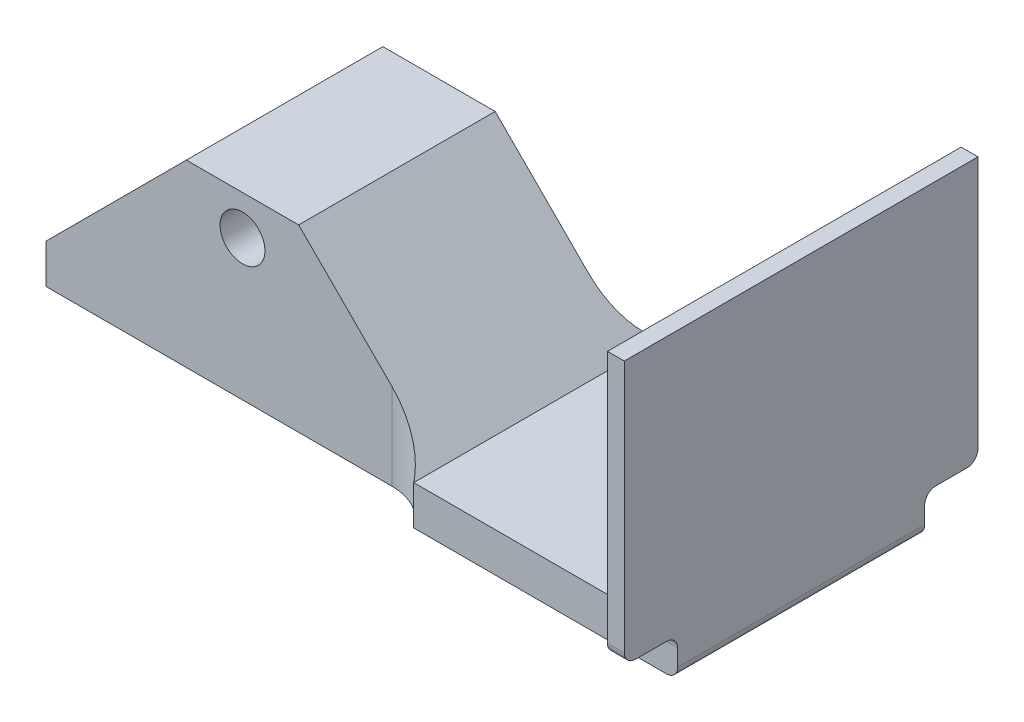
SolidWorks part; units mm, degrees
ref_plane "Front Plane" through (0, 0, 0) normal (0, 0, 1) x (1, 0, 0)
ref_plane "Top Plane" through (0, 0, 0) normal (0, 1, 0) x (1, 0, 0)
ref_plane "Right Plane" through (0, 0, 0) normal (1, 0, 0) x (0, 0, -1)
sketch "Sketch1" plane through (0, 0, 0) normal (0, 1, 0) x (1, 0, 0)
  line L1 (-35, -17.5) -> (35, -17.5)
  line L2 (-35, -17.5) -> (-35, 17.5)
  line L3 (-35, 17.5) -> (35, 17.5)
  line L4 (35, -17.5) -> (35, 17.5)
  line L5 (-35, -17.5) -> (35, 17.5) construction
  line L6 (-35, 17.5) -> (35, -17.5) construction
  point P0 (0, 0)
  dimension "D1" = 35
  dimension "D2" = 70
extrude "Boss-Extrude1" add sketch "Sketch1" along normal blind 32
sketch "Sketch2" plane through (0, 0, 17.5) normal (0, 0, 1) x (1, 0, 0)
  circle A0 centre (0, 25) radius 4
  dimension "D1" = 8
  dimension "D2" = 25
extrude "Cut-Extrude1" cut sketch "Sketch2" against normal through all
chamfer "Chamfer1" distance 25 angle 45 2 edges at (35, 32, 0) (-35, 32, 0)
sketch "Sketch3" plane through (35, 0, 0) normal (1, 0, 0) x (0, 0, -1)
  line L0 (-17.5, 0) -> (17.5, 0) construction
  line L1 (-22, 0) -> (22, 0)
  line L2 (-22, 0) -> (-22, 7)
  line L3 (-22, 7) -> (22, 7)
  line L4 (22, 0) -> (22, 7)
  point P4 (0, 7)
  dimension "D1" = 44
  dimension "D2" = 7
extrude "Boss-Extrude2" add sketch "Sketch3" along normal blind 47
fillet "Fillet1" radius 10 1 edges at (35, 3.5, -17.5)
fillet "Fillet2" radius 10 1 edges at (35, 3.5, 17.5)
sketch "Sketch4" plane through (0, 7, 0) normal (0, 1, 0) x (1, 0, 0)
  line L1 (82, 31.5) -> (79, 31.5)
  line L2 (82, 31.5) -> (82, -31.5)
  line L3 (82, -31.5) -> (79, -31.5)
  line L4 (79, 31.5) -> (79, -31.5)
  point P4 (82, 0)
  dimension "D1" = 63
  dimension "D2" = 3
extrude "Boss-Extrude3" add sketch "Sketch4" along normal blind 47
fillet "Fillet3" radius 2 5 edges at (82, 0, 0) (80.5, 7, 31.5) (80.5, 7, 22) (80.5, 7, -31.5) (80.5, 7, -22)
